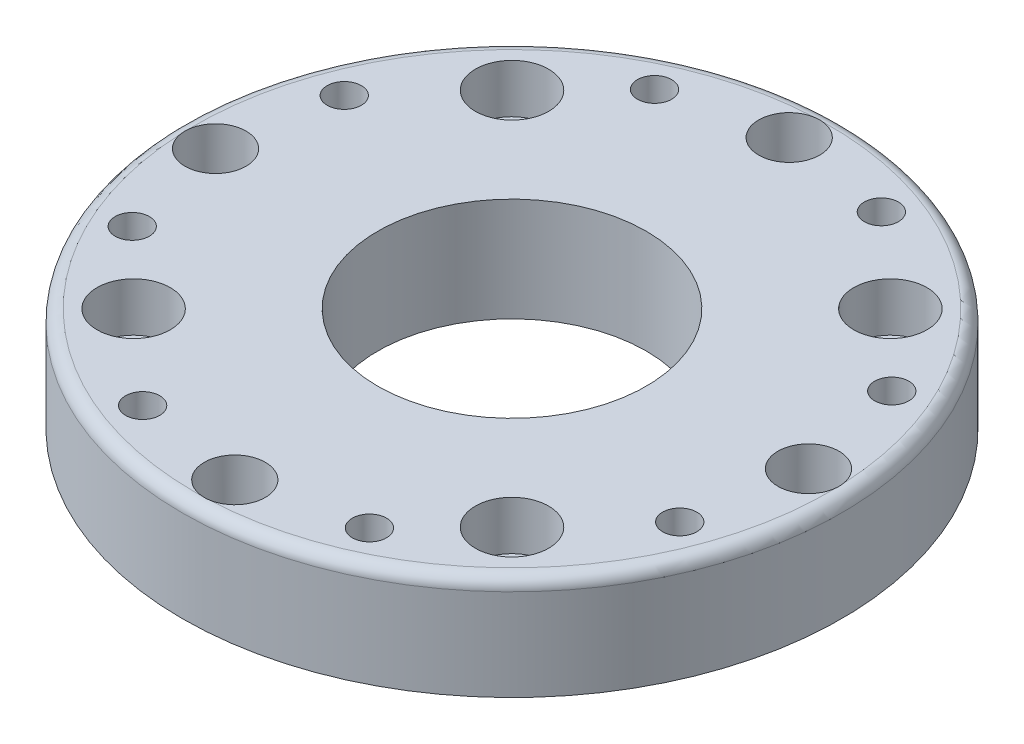
SolidWorks part; units mm, degrees
ref_plane "Front Plane" through (0, 0, 0) normal (1, 0, 0) x (0, 1, 0)
ref_plane "Top Plane" through (0, 0, 0) normal (0, 0, 1) x (0, 1, 0)
ref_plane "Right Plane" through (0, 0, 0) normal (0, 1, 0) x (-1, 0, 0)
sketch "Sketch2" plane through (0, 693.8689, 0) normal (0, 1, 0) x (-1, 0, 0)
  circle A0 centre (-1181.7984, 915.0676) radius 27
extrude "Boss-Extrude1" add sketch "Sketch2" along normal blind 8.5
sketch "Sketch3" plane through (0, 702.3689, 0) normal (0, 1, 0) x (-1, 0, 0)
  line L1 (-1197.2984, 930.5676) -> (-1166.2984, 930.5676)
  line L2 (-1197.2984, 930.5676) -> (-1197.2984, 899.5676)
  line L3 (-1197.2984, 899.5676) -> (-1166.2984, 899.5676)
  line L4 (-1166.2984, 930.5676) -> (-1166.2984, 899.5676)
  line L5 (-1197.2984, 930.5676) -> (-1166.2984, 899.5676) construction
  line L6 (-1197.2984, 899.5676) -> (-1166.2984, 930.5676) construction
  circle A0 centre (-1197.2984, 930.5676) radius 1.6
  circle A1 centre (-1166.2984, 930.5676) radius 1.6
  circle A2 centre (-1197.2984, 899.5676) radius 1.6
  circle A3 centre (-1166.2984, 899.5676) radius 1.6
  circle A5 centre (-1197.2984, 930.5676) radius 3
  circle A6 centre (-1166.2984, 930.5676) radius 3
  circle A7 centre (-1197.2984, 899.5676) radius 3
  circle A8 centre (-1166.2984, 899.5676) radius 3
  point P0 (-1181.7984, 915.0676)
  dimension "D1" = 31
  dimension "D2" = 31
extrude "Nema_Mounts_holes_M3" cut sketch "Sketch3" against normal up to surface (8.5 mm away) contours A0 | A1 | A3 | A2 up to face at (1181.7984, 693.8689, 942.0676)
extrude "Nema_Mount_holes_cap_6mm" cut sketch "Sketch3<4>" against normal blind 4 contours A5 | A6 | A7 | A8
sketch "Sketch3<4>" plane through (0, 702.3689, 0) normal (0, 1, 0) x (-1, 0, 0) same geometry as "Sketch3"
sketch "Sketch5" plane through (0, 702.3689, 0) normal (0, 1, 0) x (-1, 0, 0)
  circle A0 centre (-1160.4015, 924.7847) radius 1.4
  circle A1 centre (-1159.7975, 906.8087) radius 1.4
  circle A2 centre (-1172.0814, 893.6707) radius 1.4
  circle A3 centre (-1190.0573, 893.0667) radius 1.4
  circle A4 centre (-1203.1954, 905.3506) radius 1.4
  circle A5 centre (-1203.7994, 923.3265) radius 1.4
  circle A6 centre (-1191.5155, 936.4646) radius 1.4
  circle A7 centre (-1173.5395, 937.0686) radius 1.4
  point P20 (-1181.7984, 915.0676)
  dimension "D1" = 23.5
  dimension "D2" = 2.8
  dimension "D3" = 8
extrude "Reducer_Holes_M2.5" cut sketch "Sketch5" against normal up to surface (8.5 mm away) up to face at (1197.2984, 693.8689, 901.1676)
sketch "Sketch6" plane through (0, 693.8689, 0) normal (0, -1, 0) x (1, 0, 0)
  line L0 (1176.2363, 938.0985) -> (1173.996, 939.919)
  line L1 (1162.0943, 922.4464) -> (1163.273, 925.0816)
  line L2 (1163.273, 925.0816) -> (1161.5801, 927.4199)
  line L3 (1161.5801, 927.4199) -> (1158.7087, 927.123)
  line L4 (1158.7087, 927.123) -> (1157.5301, 924.4878)
  line L5 (1157.5301, 924.4878) -> (1159.2229, 922.1495)
  line L6 (1159.2229, 922.1495) -> (1162.0943, 922.4464)
  line L7 (1173.996, 939.919) -> (1171.2992, 938.8891)
  line L8 (1171.2992, 938.8891) -> (1170.8428, 936.0386)
  line L9 (1170.8428, 936.0386) -> (1173.0831, 934.2181)
  line L10 (1173.0831, 934.2181) -> (1175.7799, 935.2481)
  line L11 (1175.7799, 935.2481) -> (1176.2363, 938.0985)
  line L12 (1194.1507, 935.2859) -> (1193.8538, 938.1574)
  line L13 (1193.8538, 938.1574) -> (1191.2186, 939.336)
  line L14 (1191.2186, 939.336) -> (1188.8803, 937.6432)
  line L15 (1188.8803, 937.6432) -> (1189.1772, 934.7718)
  line L16 (1189.1772, 934.7718) -> (1191.8124, 933.5931)
  line L17 (1191.8124, 933.5931) -> (1194.1507, 935.2859)
  line L18 (1204.8293, 920.6298) -> (1206.6498, 922.8701)
  line L19 (1206.6498, 922.8701) -> (1205.6199, 925.5669)
  line L20 (1205.6199, 925.5669) -> (1202.7694, 926.0233)
  line L21 (1202.7694, 926.0233) -> (1200.9489, 923.783)
  line L22 (1200.9489, 923.783) -> (1201.9789, 921.0862)
  line L23 (1201.9789, 921.0862) -> (1204.8293, 920.6298)
  line L24 (1202.0167, 902.7154) -> (1204.8882, 903.0123)
  line L25 (1204.8882, 903.0123) -> (1206.0668, 905.6474)
  line L26 (1206.0668, 905.6474) -> (1204.374, 907.9857)
  line L27 (1204.374, 907.9857) -> (1201.5026, 907.6889)
  line L28 (1201.5026, 907.6889) -> (1200.3239, 905.0537)
  line L29 (1200.3239, 905.0537) -> (1202.0167, 902.7154)
  line L30 (1187.3606, 892.0368) -> (1189.6009, 890.2163)
  line L31 (1189.6009, 890.2163) -> (1192.2977, 891.2462)
  line L32 (1192.2977, 891.2462) -> (1192.7541, 894.0967)
  line L33 (1192.7541, 894.0967) -> (1190.5138, 895.9172)
  line L34 (1190.5138, 895.9172) -> (1187.817, 894.8872)
  line L35 (1187.817, 894.8872) -> (1187.3606, 892.0368)
  line L36 (1169.4462, 894.8493) -> (1169.7431, 891.9779)
  line L37 (1169.7431, 891.9779) -> (1172.3782, 890.7993)
  line L38 (1172.3782, 890.7993) -> (1174.7166, 892.4921)
  line L39 (1174.7166, 892.4921) -> (1174.4197, 895.3635)
  line L40 (1174.4197, 895.3635) -> (1171.7845, 896.5422)
  line L41 (1171.7845, 896.5422) -> (1169.4462, 894.8493)
  line L42 (1158.7676, 909.5055) -> (1156.9471, 907.2652)
  line L43 (1156.9471, 907.2652) -> (1157.977, 904.5684)
  line L44 (1157.977, 904.5684) -> (1160.8275, 904.112)
  line L45 (1160.8275, 904.112) -> (1162.648, 906.3523)
  line L46 (1162.648, 906.3523) -> (1161.618, 909.0491)
  line L47 (1161.618, 909.0491) -> (1158.7676, 909.5055)
  circle A0 centre (1160.4015, 924.7847) radius 2.5 construction
  point P1 (1158.1194, 925.8054)
  point P54 (1181.7984, 915.0676)
  dimension "D1" = 5
  dimension "D2" = 8
extrude "Reducer_Nuts_M2.5" cut sketch "Sketch6" against normal blind 4
sketch "Sketch9" plane through (0, 693.8689, 0) normal (0, -1, 0) x (-1, 0, 0)
  circle A1 centre (-1181.7984, -915.0676) radius 11
  dimension "D1" = 22
extrude "Shaft_skirt_22mm" cut sketch "Sketch9" against normal up to surface (8.5 mm away) up to face at (1173.5395, 702.3689, 938.4686)
fillet "Fillet1" radius 1 1 edges at (1181.7984, 702.3689, 942.0676)
sketch "Sketch10" plane through (0, 693.8689, 0) normal (0, -1, 0) x (1, 0, 0)
  line L0 (1172.1395, 937.0686) -> (1192.9155, 936.4646) construction
  line L1 (1192.9155, 936.4646) -> (1182.5275, 936.7666) construction
  line L2 (1182.5275, 936.7666) -> (1182.7058, 942.0524) construction
  circle A0 centre (1182.5883, 938.5676) radius 2.5
  circle A1 centre (1181.7984, 915.0676) radius 27 construction
  circle A2 centre (1173.5395, 937.0686) radius 1.4 construction
  circle A3 centre (1191.5155, 936.4646) radius 1.4 construction
  circle A4 centre (1205.2984, 914.2778) radius 2.5
  circle A5 centre (1181.0086, 891.5676) radius 2.5
  circle A6 centre (1158.2984, 915.8575) radius 2.5
  point P21 (1181.7984, 915.0676)
  dimension "D1" = 23.5
  dimension "D2" = 4
sketch "Sketch11" plane through (0, 693.8689, 0) normal (0, -1, 0) x (-1, 0, 0)
  point P0 (-1173.5395, -937.0686)
  point P1 (-1191.5155, -936.4646)
extrude "Cut-Extrude1" cut sketch "Sketch10" along normal blind 5 from surface starting at face at (1181.7984, 702.3689, 941.0676)
fillet "Fillet3" radius 1 4 edges at (1205.2984, 697.3689, 916.7778) (1181.0086, 697.3689, 894.0676) (1158.2984, 697.3689, 918.3575) (1182.5883, 697.3689, 941.0676)
